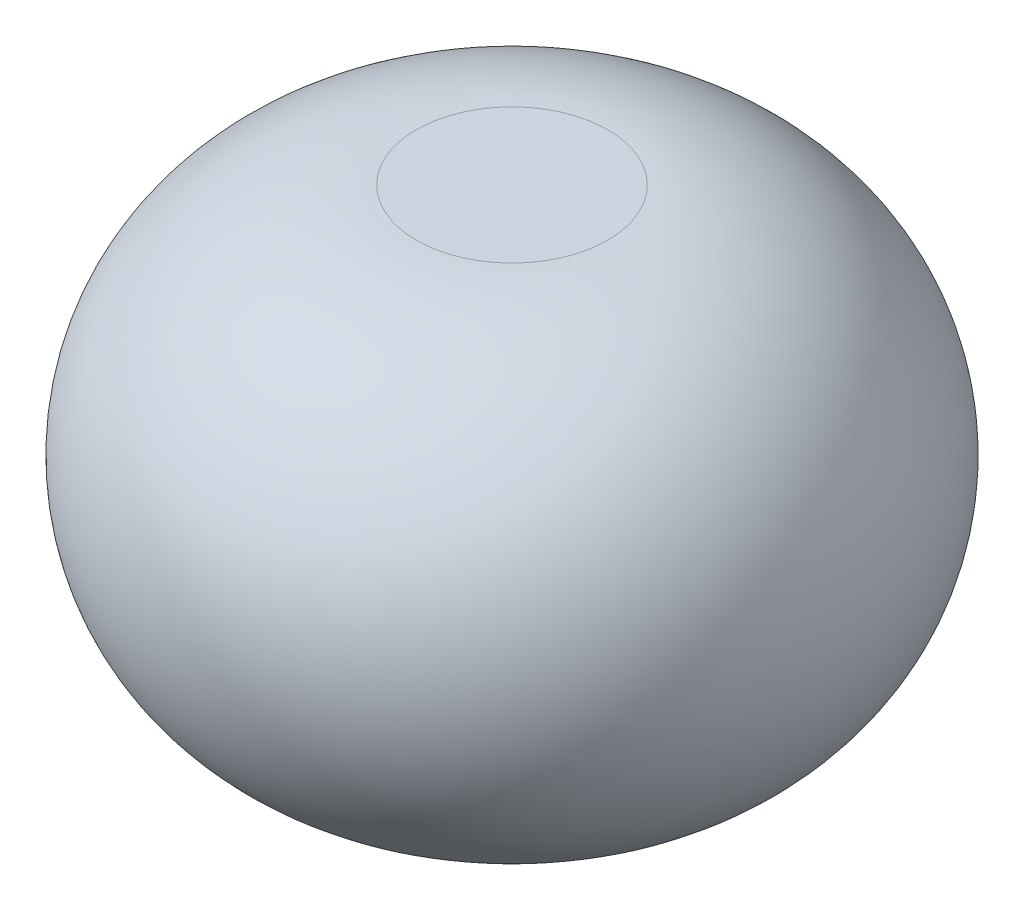
SolidWorks part; units mm, degrees
ref_plane "Front Plane" through (0, 0, 0) normal (0, 0, 1) x (1, 0, 0)
ref_plane "Top Plane" through (0, 0, 0) normal (0, 1, 0) x (1, 0, 0)
ref_plane "Right Plane" through (0, 0, 0) normal (1, 0, 0) x (0, 0, -1)
sketch "Sketch1" plane through (0, 0, 0) normal (0, 0, 1) x (1, 0, 0)
  line L0 (0, -31.0382) -> (0, 1520.8727) construction
  line L1 (0, 24) -> (24, 24) construction
  line L2 (24, 24) -> (24, 21) construction
  line L3 (9, -24) -> (0, -24) construction
  line L4 (0, 23) -> (9, 23)
  line L5 (0, 23) -> (0, -21)
  line L6 (9, -21) -> (0, -21)
  arc A0 (9, 23) -> (9, -21) centre (9, 1) cw
  arc A1 (24, 21) -> (9, -24) centre (9, 1) cw construction
  dimension "D4" = 25
  dimension "D6" = 44
  dimension "D1" = 24
  dimension "D2" = 24
  dimension "D3" = 3
  dimension "D5" = 48
revolve "Revolve1" add sketch "Sketch1" angle 360 about L0
ref_axis "Axis1" through (-34.1, 0, 0) along (1, 0, 0)
ref_axis "Axis2" through (0, -23.2, 0) along (0, 1, 0)
